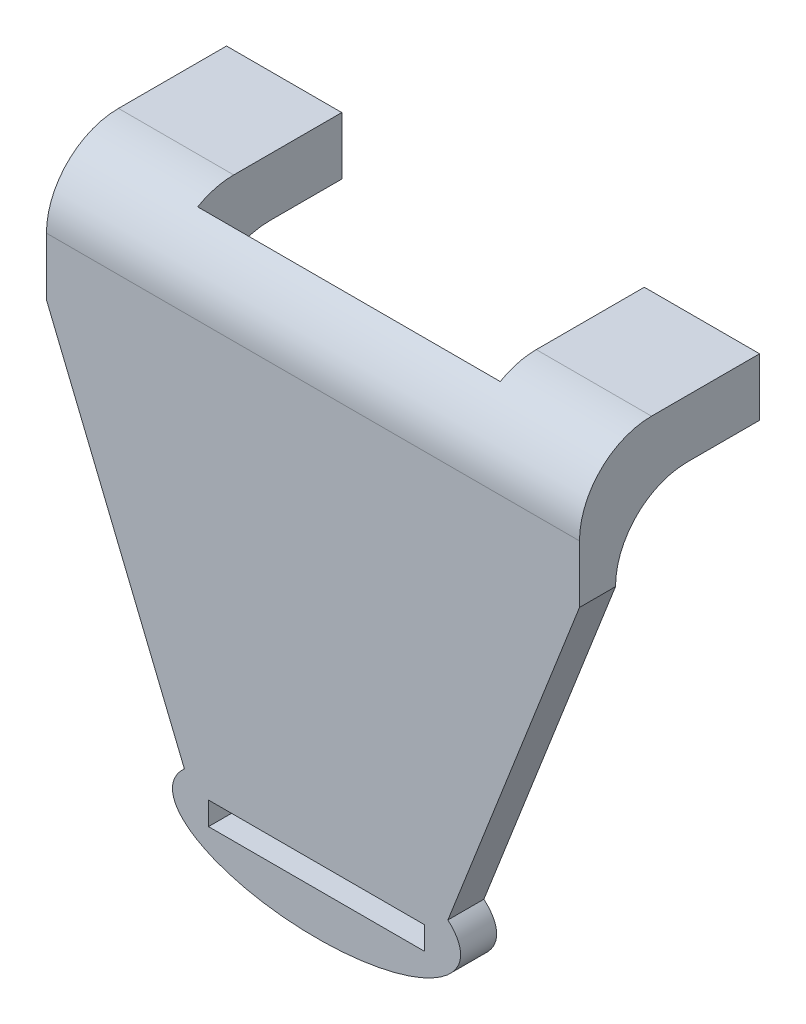
SolidWorks part; units mm, degrees
ref_plane "Front Plane" through (0, 0, 0) normal (0, 0, 1) x (1, 0, 0)
ref_plane "Top Plane" through (0, 0, 0) normal (0, 1, 0) x (1, 0, 0)
ref_plane "Right Plane" through (0, 0, 0) normal (1, 0, 0) x (0, 0, -1)
sketch "Plate Feature Sketch" plane through (0, 0, 0) normal (0, 0, 1) x (1, 0, 0)
  line L0 (-36, 18) -> (-36, 0)
  line L4 (38, 0) -> (38, 18)
  line L5 (38, 18) -> (-36, 18)
  line L6 (-36, 0) -> (-15.5537, -50)
  line L7 (-15.5537, -50) -> (18.4463, -50)
  line L8 (18.4463, -50) -> (38, 0)
  dimension "D1" = 68
  dimension "D2" = 34
  dimension "D3" = 74
extrude "Plate Feature" add sketch "Plate Feature Sketch" along normal blind 5 contours L8 L4 L5 L0 L6 L7
sketch "Strap Feature Sketch" plane through (0, 0, 0) normal (0, 0, 1) x (1, 0, 0)
  ellipse E0 centre (1.5, -50) end of major axis (21.5, -50) minor radius 8
extrude "Strap Feature" add sketch "Strap Feature Sketch" along normal blind 5 contours E0
sketch "Strap Cut Sketch" plane through (0, 0, 0) normal (0, 0, 1) x (1, 0, 0)
  line L1 (-13.5, -48.9009) -> (16.5, -48.9009)
  line L2 (-13.5, -48.9009) -> (-13.5, -52.0991)
  line L3 (-13.5, -52.0991) -> (16.5, -52.0991)
  line L4 (16.5, -48.9009) -> (16.5, -52.0991)
  line L5 (-13.5, -48.9009) -> (16.5, -52.0991) construction
  line L6 (-13.5, -52.0991) -> (16.5, -48.9009) construction
  point P0 (1.5, -50.5)
  point P5 (0, 0)
  point P6 (0, 0)
  point P7 (0, 0)
  dimension "D1" = 30
  dimension "D2" = 3.1982
extrude "Strap Cut" cut sketch "Strap Cut Sketch" along normal blind 5
sketch "Left Leg Feature Sketch" plane through (0, 0, 0) normal (0, 0, 1) x (1, 0, 0)
  line L0 (38, 10) -> (22, 10)
  line L1 (38, 10) -> (38, 18)
  line L2 (22, 10) -> (22, 18)
  line L3 (38, 18) -> (22, 18)
  line L4 (38, 0) -> (38, 18) construction
  line L5 (38, 18) -> (-36, 18) construction
  dimension "D1" = 0
  dimension "D2" = 8
  dimension "D3" = 0
extrude "Left Leg Feature" add sketch "Left Leg Feature Sketch" against normal blind 20 contours L2 L3 L1 L0
sketch "Right Leg Feature Sketch" plane through (0, 0, 0) normal (0, 0, 1) x (1, 0, 0)
  line L0 (-36, 10) -> (-20, 10)
  line L1 (-36, 10) -> (-36, 18)
  line L2 (-20, 10) -> (-20, 18)
  line L3 (-36, 18) -> (-20, 18)
  line L5 (38, 18) -> (-36, 18) construction
  dimension "D1" = 0
  dimension "D2" = 8
extrude "Right Leg Feature" add sketch "Right Leg Feature Sketch" against normal blind 20 contours L0 L2 L3 L1
sketch "Tab Cut Sketch" plane through (0, 10, 0) normal (0, 1, 0) x (1, 0, 0)
  line L0 (-36, -5) -> (-36, 20) construction
  line L1 (-32, 20) -> (-24, 20)
  line L2 (-32, 20) -> (-32, 5)
  line L3 (-32, 5) -> (-24, 5)
  line L4 (-24, 20) -> (-24, 5)
  line L5 (-32, 20) -> (-24, 5) construction
  line L6 (-32, 5) -> (-24, 20) construction
  line L7 (22, 20) -> (22, 0) construction
  line L8 (26, 20) -> (34, 20)
  line L9 (26, 20) -> (26, 5)
  line L10 (26, 5) -> (34, 5)
  line L11 (34, 20) -> (34, 5)
  line L12 (26, 20) -> (34, 5) construction
  line L13 (26, 5) -> (34, 20) construction
  point P0 (-28, 12.5)
  point P5 (30, 12.5)
  dimension "D1" = 8
  dimension "D2" = 15
  dimension "D3" = 4
  dimension "D4" = 8
  dimension "D5" = 4
extrude "Tab Cut" cut sketch "Tab Cut Sketch" along normal blind 5
fillet "Fillet1" radius 10 1 edges at (1, 18, 5)
fillet "Fillet2" radius 10 1 edges at (-28, 10, 0)
fillet "Fillet3" radius 10 1 edges at (30, 10, 0)
